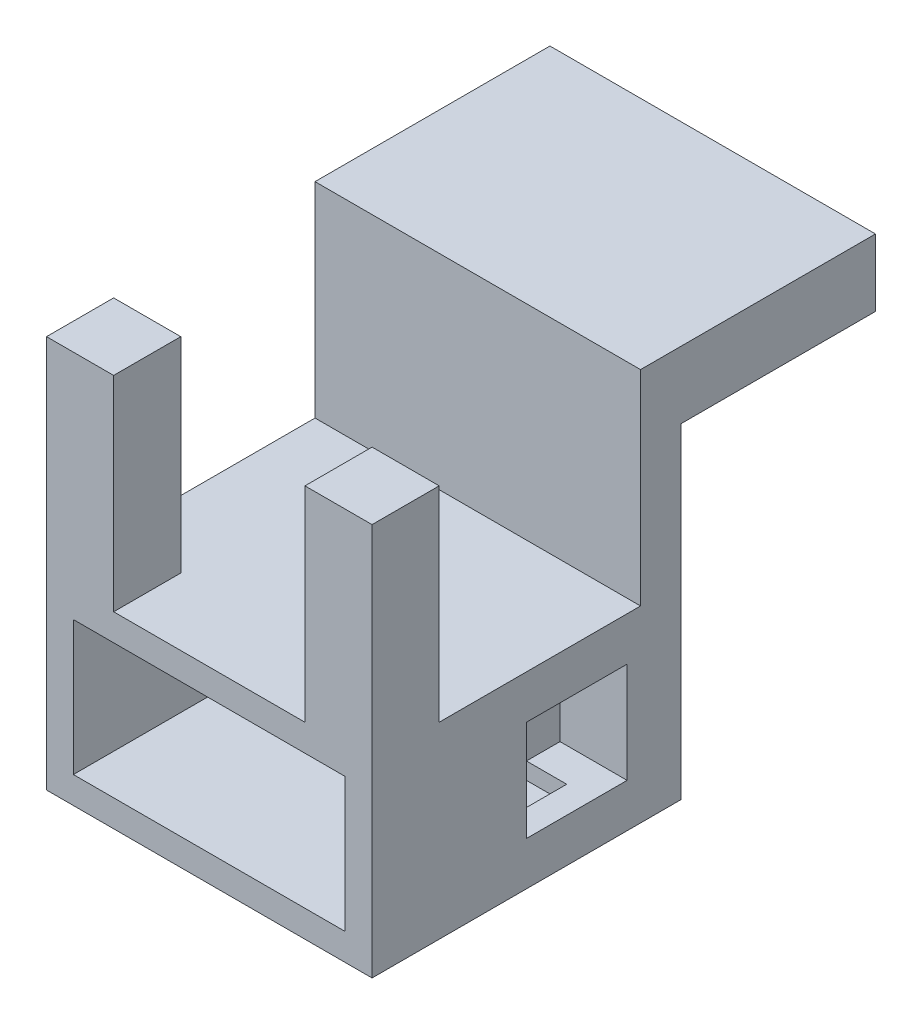
SolidWorks part; units mm, degrees
ref_plane "Front Plane" through (0, 0, 0) normal (0, 0, 1) x (1, 0, 0)
ref_plane "Top Plane" through (0, 0, 0) normal (0, 1, 0) x (1, 0, 0)
ref_plane "Right Plane" through (0, 0, 0) normal (1, 0, 0) x (0, 0, -1)
sketch "Sketch1" plane through (0, 0, -17.55) normal (0, 0, -1) x (-1, 0, 0)
  line L0 (9.25, 9.75) -> (-29.75, 9.75) construction
  line L1 (-30.5, 10) -> (10, 10)
  line L2 (-30.5, 10) -> (-30.5, -10)
  line L3 (-30.5, -10) -> (10, -10)
  line L4 (10, 10) -> (10, -10)
  line L5 (-30.5, 10) -> (10, -10) construction
  line L6 (-30.5, -10) -> (10, 10) construction
  line L7 (9.75, 3.5) -> (9.75, -3.5) construction
  line L8 (-29.75, -9.75) -> (9.25, -9.75) construction
  line L9 (-30.25, 9.25) -> (-30.25, -9.25) construction
  line L10 (-34.5, 14) -> (14, 14)
  line L11 (14, 14) -> (14, -14)
  line L12 (-34.5, -14) -> (14, -14)
  line L13 (-34.5, 14) -> (-34.5, -14)
  point P0 (-10.25, 0)
  dimension "D1" = 0.25
  dimension "D2" = 0.25
  dimension "D3" = 0.25
  dimension "D4" = 0.25
  dimension "D5" = 4
extrude "Boss-Extrude1" add sketch "Sketch1" along normal blind 40
sketch "Sketch2" plane through (0, 0, -57.55) normal (0, 0, -1) x (-1, 0, 0)
  line L1 (-34.5, 14) -> (14, 14)
  line L2 (-34.5, 14) -> (-34.5, -14)
  line L3 (-34.5, -14) -> (14, -14)
  line L4 (14, 14) -> (14, -14)
extrude "Boss-Extrude2" add sketch "Sketch2" against normal blind 7
sketch "Sketch3" plane through (34.5, 0, 0) normal (1, 0, 0) x (0, 0, -1)
  line L1 (40.55, 7.5) -> (55.55, 7.5)
  line L2 (40.55, 7.5) -> (40.55, -7.5)
  line L3 (40.55, -7.5) -> (55.55, -7.5)
  line L4 (55.55, 7.5) -> (55.55, -7.5)
  line L5 (57.55, 14) -> (57.55, -14) construction
  line L6 (40.55, 0) -> (55.55, 0) construction
  dimension "D1" = 2
  dimension "D2" = 15
  dimension "D3" = 15
extrude "Cut-Extrude1" cut sketch "Sketch3" against normal blind 10
sketch "Sketch4" plane through (0, 0, -57.55) normal (0, 0, -1) x (-1, 0, 0)
  line L0 (-34.5, -14) -> (14, -14) construction
  line L1 (14, 14) -> (-34.5, 14)
  line L2 (14, 14) -> (14, 34.5)
  line L3 (14, 34.5) -> (-34.5, 34.5)
  line L4 (-34.5, 14) -> (-34.5, 34.5)
  line L6 (-34.5, 14) -> (-34.5, -14) construction
  line L8 (-34.5, 34.5) -> (14, 34.5)
  line L9 (-34.5, 34.5) -> (-34.5, 44.5)
  line L10 (-34.5, 44.5) -> (14, 44.5)
  line L11 (14, 34.5) -> (14, 44.5)
  line M4 (-34.5, 14) -> (-34.5, -14)
  line M5 (-34.5, -14) -> (14, -14)
  line M6 (14, -14) -> (14, 14)
  line M7 (14, 14) -> (-34.5, 14)
  dimension "D1" = 48.5
  dimension "D2" = 10
extrude "Boss-Extrude3" add sketch "Sketch4" along normal blind 6 contours M7 M4 M5 M6 | L4 L10 L2 M5 | L10 L4 L3 L2 | L4 L2 L3 M7 region at (10.25, 0, -57.55) region at (10.25, 24.25, -57.55) region at (10.25, 39.5, -57.55)
extrude "Boss-Extrude4" add sketch "Sketch4<3>" along normal blind 35 contours L10 L4 L3 L2 region at (10.25, 39.5, -57.55)
sketch "Sketch4<3>" plane through (0, 0, -57.55) normal (0, 0, -1) x (-1, 0, 0) same geometry as "Sketch4"
sketch "Sketch5" plane through (0, 14, 0) normal (0, -1, 0) x (1, 0, 0)
  line L1 (-14, -17.55) -> (-4, -17.55)
  line L2 (-14, -17.55) -> (-14, -27.55)
  line L3 (-14, -27.55) -> (-4, -27.55)
  line L4 (-4, -17.55) -> (-4, -27.55)
  line L5 (34.5, -17.55) -> (24.5, -17.55)
  line L6 (34.5, -17.55) -> (34.5, -27.55)
  line L7 (34.5, -27.55) -> (24.5, -27.55)
  line L8 (24.5, -17.55) -> (24.5, -27.55)
  dimension "D1" = 10
  dimension "D2" = 10
  dimension "D3" = 10
extrude "Boss-Extrude5" add sketch "Sketch5" against normal up to surface (30.5 mm away) up to face at (10.25, 44.5, -75.05)
